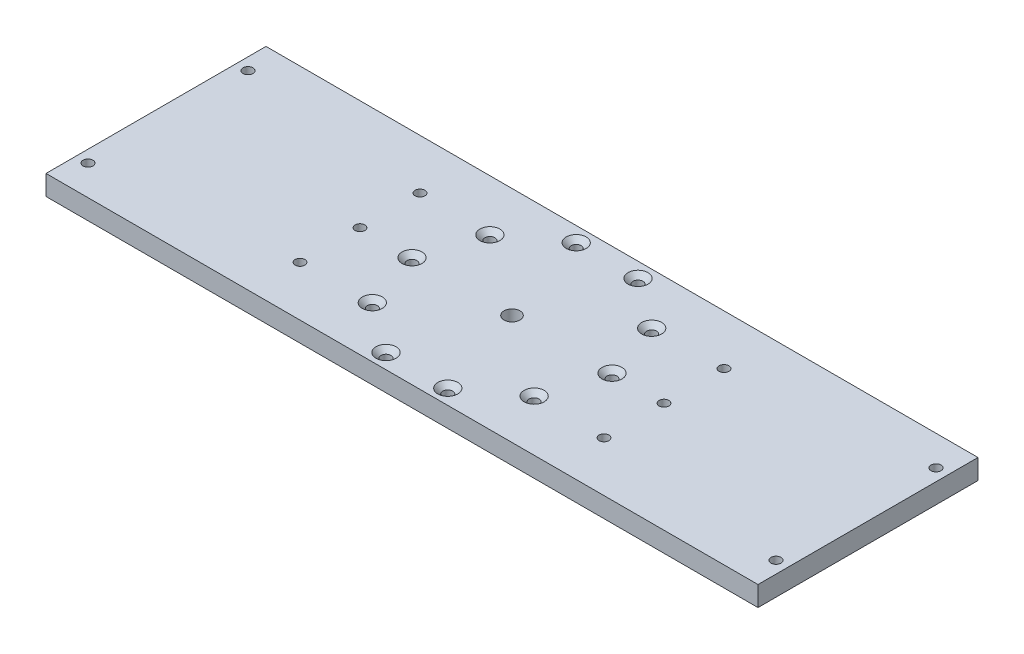
SolidWorks part; units mm, degrees
ref_plane "Ebene vorne" through (0, 0, 0) normal (0, 0, 1) x (1, 0, 0)
ref_plane "Ebene oben" through (0, 0, 0) normal (0, 1, 0) x (1, 0, 0)
ref_plane "Ebene rechts" through (0, 0, 0) normal (1, 0, 0) x (0, 0, -1)
sketch "Skizze3" plane through (0, 0, 0) normal (0, 1, 0) x (1, 0, 0)
  line L0 (0, 0) -> (356, 0)
  line L1 (356, 0) -> (356, 110)
  line L2 (356, 110) -> (0, 110)
  line L3 (0, 110) -> (0, 0)
  dimension "D1" = 110
  dimension "D2" = 356
extrude "Aufsatz-Linear austragen1" add sketch "Skizze3" along normal blind 10
sketch "Skizze4" plane through (0, 10, 0) normal (0, 1, 0) x (1, 0, 0)
  line L0 (0, 110) -> (356, 0) construction
  line L1 (0, 0) -> (356, 110) construction
  circle A0 centre (178, 55) radius 50 construction
  circle A1 centre (128, 55) radius 2.5
  circle A2 centre (178, 55) radius 50 construction
  circle A3 centre (137.5492, 84.3893) radius 2.5
  circle A4 centre (178, 55) radius 50 construction
  circle A5 centre (162.5492, 102.5528) radius 2.5
  circle A6 centre (178, 55) radius 50 construction
  circle A7 centre (193.4508, 102.5528) radius 2.5
  circle A8 centre (178, 55) radius 50 construction
  circle A9 centre (218.4508, 84.3893) radius 2.5
  circle A10 centre (178, 55) radius 50 construction
  circle A11 centre (228, 55) radius 2.5
  circle A12 centre (178, 55) radius 50 construction
  circle A13 centre (218.4508, 25.6107) radius 2.5
  circle A14 centre (178, 55) radius 50 construction
  circle A15 centre (193.4508, 7.4472) radius 2.5
  circle A16 centre (178, 55) radius 50 construction
  circle A17 centre (162.5492, 7.4472) radius 2.5
  circle A18 centre (178, 55) radius 50 construction
  circle A19 centre (137.5492, 25.6107) radius 2.5
  dimension "D1" = 100
  dimension "D2" = 5
  dimension "D3" = 10
extrude "Schnitt-Linear austragen1" cut sketch "Skizze4" against normal through all
sketch "Skizze5" plane through (0, 10, 0) normal (0, 1, 0) x (1, 0, 0)
  line L0 (0, 110) -> (356, 0) construction
  line L1 (0, 0) -> (356, 110) construction
  line L2 (356, 110) -> (0, 110) construction
  line L3 (112, 0) -> (244, 0) construction
  line L4 (112, 0) -> (112, 110) construction
  line L5 (112, 110) -> (244, 110) construction
  line L6 (244, 0) -> (244, 110) construction
  line L7 (112, 0) -> (244, 110) construction
  line L8 (112, 110) -> (244, 0) construction
  line L9 (0, 0) -> (356, 0) construction
  line L10 (112, 110) -> (92, 110) construction
  line L11 (112, 110) -> (112, 0) construction
  line L12 (112, 0) -> (92, 0) construction
  line L13 (92, 110) -> (92, 0) construction
  line L14 (0, 55) -> (50000, 55) construction
  line L15 (244, 0) -> (264, 0) construction
  line L16 (244, 0) -> (244, 110) construction
  line L17 (244, 110) -> (264, 110) construction
  line L18 (264, 0) -> (264, 110) construction
  line L19 (0, 110) -> (0, 0) construction
  line L20 (102, 110) -> (102, 0) construction
  line L21 (254, 110) -> (254, 0) construction
  circle A0 centre (102, 85) radius 2.45
  circle A1 centre (102, 25) radius 2.45
  circle A2 centre (254, 25) radius 2.45
  circle A3 centre (254, 85) radius 2.45
  circle A4 centre (102, 55) radius 2.45
  circle A5 centre (254, 55) radius 2.45
  point P8 (178, 55)
  point P25 (0, 55)
  dimension "D4" = 4.9
  dimension "D1" = 132
  dimension "D2" = 20
  dimension "D3" = 20
  dimension "D5" = 30
  dimension "D6" = 30
  dimension "D7" = 30
  dimension "D8" = 30
extrude "Schnitt-Linear austragen2" cut sketch "Skizze5" against normal through all
ref_plane "Ebene1" through (0, 0, -55) normal (0, 0, -1) x (-1, 0, 0)
sketch "Skizze7" plane through (0, 10, 0) normal (0, 1, 0) x (1, 0, 0)
  line L0 (0, 110) -> (356, 0) construction
  line L1 (0, 0) -> (356, 110) construction
  line L2 (356, 110) -> (0, 110) construction
  line L3 (92, 0) -> (264, 0) construction
  line L4 (92, 0) -> (92, 110) construction
  line L5 (92, 110) -> (264, 110) construction
  line L6 (264, 0) -> (264, 110) construction
  line L7 (92, 0) -> (264, 110) construction
  line L8 (92, 110) -> (264, 0) construction
  line L9 (0, 0) -> (356, 0) construction
  line L10 (344, 110) -> (356, 110) construction
  line L11 (344, 110) -> (344, 0) construction
  line L12 (344, 0) -> (356, 0) construction
  line L13 (356, 110) -> (356, 0) construction
  line L14 (175, 55) -> (-49825, 55) construction
  line L15 (0, 110) -> (12, 110) construction
  line L16 (0, 110) -> (0, 0) construction
  line L17 (0, 0) -> (12, 0) construction
  line L18 (12, 110) -> (12, 0) construction
  line L19 (6, 0) -> (6, 50000) construction
  line L20 (350, 0) -> (350, 50000) construction
  circle A0 centre (6, 95) radius 2.5
  circle A2 centre (6, 15) radius 2.5
  circle A3 centre (350, 15) radius 2.5
  circle A5 centre (350, 95) radius 2.5
  point P8 (178, 55)
  point P27 (6, 0)
  point P30 (350, 0)
  dimension "D5" = 5
  dimension "D1" = 172
  dimension "D2" = 80
  dimension "D3" = 12
  dimension "D4" = 80
  dimension "D6" = 40
  dimension "D7" = 40
  dimension "D8" = 40
  dimension "D9" = 40
extrude "Schnitt-Linear austragen3" cut sketch "Skizze7" against normal through all
hole_wizard "Ø8.0 (8) Durchmesser Bohrung1" positions "Skizze8" profile "Skizze9" hole size "Ø8.0" standard "DIN" end condition through all
sketch "Skizze8" plane through (0, 10, 0) normal (0, 1, 0) x (1, 0, 0)
  line L0 (356, 110) -> (0, 110) construction
  line L1 (356, 0) -> (356, 110) construction
  point P0 (178, 55)
  dimension "D1" = 55
  dimension "D2" = 178
sketch "Skizze9" plane through (178, 10, -55) normal (1, 0, 0) x (0, 0, 1)
  line L0 (0, 0) -> (0, 10)
  line L1 (0, 10) -> (4, 10)
  line L2 (4, 10) -> (4, 0)
  line L5 (4, 0) -> (0, 0)
  line L11 (0, -6.35) -> (0, 107.95) construction
  dimension "Bohrerdurchmesser" = 8
  dimension "Bohrungstiefe" = 10
chamfer "Fase1" distance 2.5 angle 45 10 edges at (193.4508, 10, -100.0528) (218.4508, 10, -81.8893) (228, 10, -52.5) (218.4508, 10, -23.1107) (193.4508, 10, -4.9472) (162.5492, 10, -4.9472) (137.5492, 10, -23.1107) (128, 10, -52.5) (137.5492, 10, -81.8893) (162.5492, 10, -100.0528)
chamfer "Fase2" distance 2.5 angle 45 10 edges at (350, 0, -92.5) (350, 0, -12.5) (254, 0, -82.55) (254, 0, -52.55) (6, 0, -12.5) (6, 0, -92.5) (102, 0, -82.55) (102, 0, -52.55) (102, 0, -22.55) (254, 0, -22.55)
